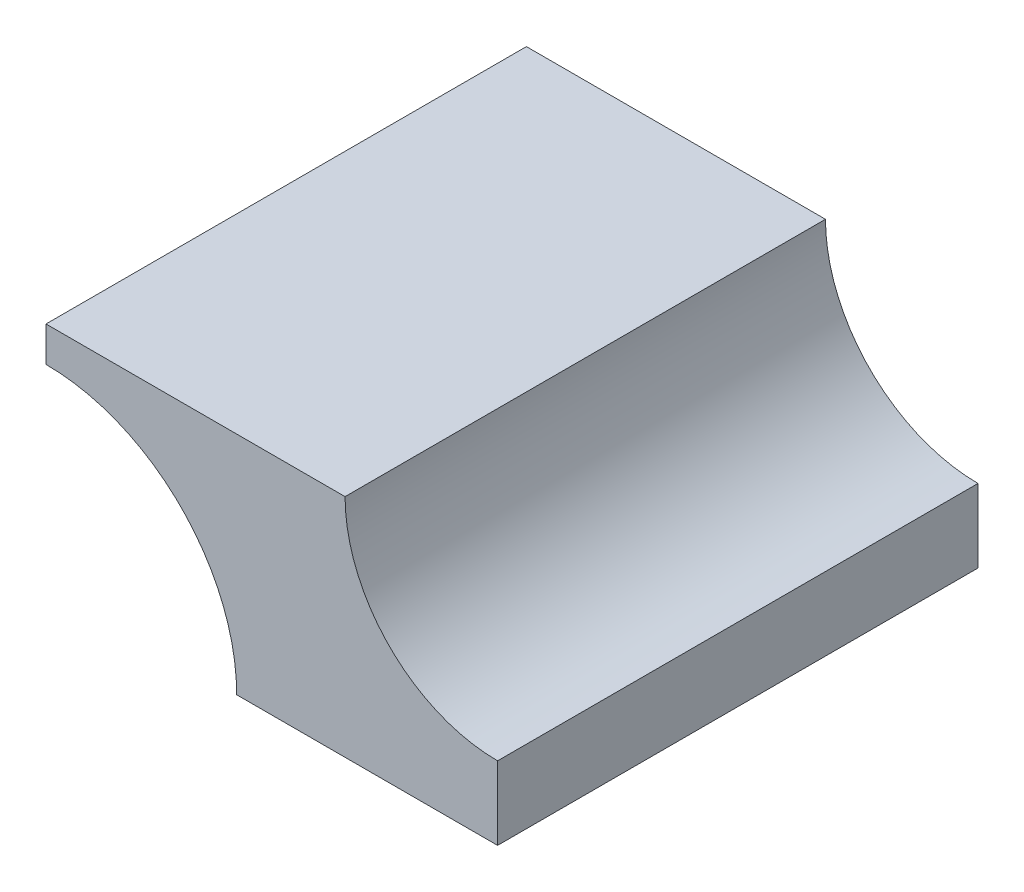
SolidWorks part; units mm, degrees
ref_plane "Front Plane" through (0, 0, 0) normal (0, 0, 1) x (1, 0, 0)
ref_plane "Top Plane" through (0, 0, 0) normal (0, 1, 0) x (1, 0, 0)
ref_plane "Right Plane" through (0, 0, 0) normal (1, 0, 0) x (0, 0, -1)
sketch "Sketch1" plane through (0, 0, 0) normal (0, 0, 1) x (1, 0, 0)
  line L1 (7.94, 0) -> (18.8, 0)
  line L2 (0, 7.94) -> (0, 9.4)
  line L3 (0, 9.4) -> (12.45, 9.4)
  line L4 (18.8, 0) -> (18.8, 3.05)
  arc A0 (7.94, 0) -> (0, 7.94) centre (0, 0) ccw
  arc A1 (12.45, 9.4) -> (18.8, 3.05) centre (18.8, 9.4) ccw
  dimension "D3" = 7.94
  dimension "D4" = 6.35
  dimension "D1" = 18.8
  dimension "D2" = 9.4
extrude "Boss-Extrude1" add sketch "Sketch1" along normal blind 20
equation "\"CoolantRadius\"= 7.94mm"
equation "\"FuelRadius\"= 6.35mm"
equation "\"D3@Sketch1\"=\"CoolantRadius\""
equation "\"D4@Sketch1\"=\"FuelRadius\""
